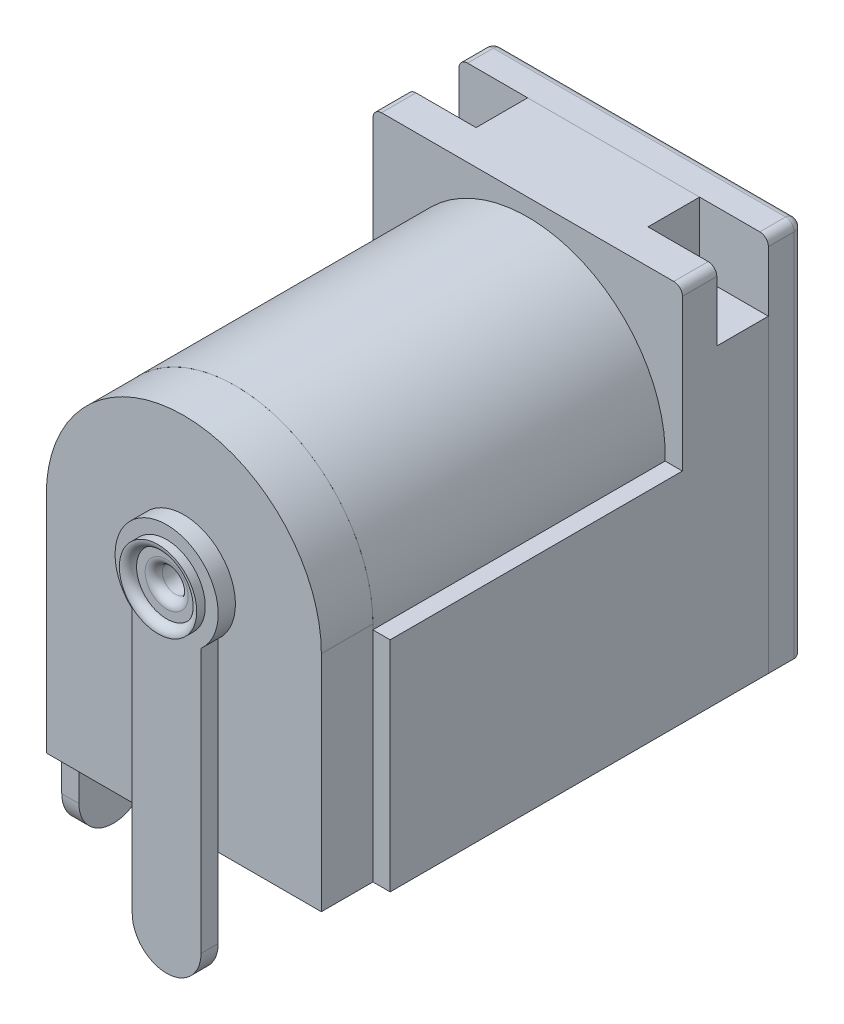
SolidWorks part; units mm, degrees
ref_plane "Front Plane" through (0, 0, 0) normal (0, 0, 1) x (1, 0, 0)
ref_plane "Top Plane" through (0, 0, 0) normal (0, 1, 0) x (1, 0, 0)
ref_plane "Right Plane" through (0, 0, 0) normal (1, 0, 0) x (0, 0, -1)
sketch "Sketch1" plane through (0, 0, 0) normal (0, 0, 1) x (1, 0, 0)
  line L1 (4.5, -3.175) -> (-4.5, -3.175)
  line L2 (4.5, -3.175) -> (4.5, 3.175)
  line L3 (4.5, 3.175) -> (-4.5, 3.175)
  line L4 (-4.5, -3.175) -> (-4.5, 3.175)
  line L5 (4.5, -3.175) -> (-4.5, 3.175) construction
  line L6 (4.5, 3.175) -> (-4.5, -3.175) construction
  point P0 (0, 0)
  dimension "D1" = 6.35
  dimension "D2" = 9
extrude "Boss-Extrude1" add sketch "Sketch1" along normal blind 12
sketch "Sketch2" plane through (0, 0, 0) normal (0, 0, -1) x (-1, 0, 0)
  line L1 (4.5, 7.825) -> (-4.5, 7.825)
  line L2 (4.5, 7.825) -> (4.5, -3.175)
  line L3 (4.5, -3.175) -> (-4.5, -3.175)
  line L4 (-4.5, 7.825) -> (-4.5, -3.175)
  line L5 (4.5, 7.825) -> (-4.5, -3.175) construction
  line L6 (4.5, -3.175) -> (-4.5, 7.825) construction
  point P0 (0, 2.325)
  dimension "D1" = 11
extrude "Boss-Extrude2" add sketch "Sketch2" against normal blind 3.5
sketch "Sketch4" plane through (0, 0, 0) normal (0, 0, -1) x (-1, 0, 0)
  line L1 (4.5, 7.825) -> (-4.5, 7.825) construction
  circle A0 centre (0, 3.325) radius 4
  point P6 (0, 7.325)
  dimension "D1" = 8
  dimension "D2" = 0.5
extrude "Boss-Extrude3" add sketch "Sketch4" against normal up to surface (12 mm away) up to face at (0, 0, 12)
ref_plane "Plane1" through (0, 0, 1.75) normal (0, 0, 1) x (1, 0, 0)
sketch "Sketch5" plane through (0, 0, 1.75) normal (0, 0, 1) x (1, 0, 0)
  line L0 (0, 0) -> (0, 7.825) construction
  line L1 (-2.5, 5.825) -> (-4.5, 5.825)
  line L2 (-2.5, 5.825) -> (-2.5, 7.825)
  line L3 (-2.5, 7.825) -> (-4.5, 7.825)
  line L4 (-4.5, 5.825) -> (-4.5, 7.825)
  line L5 (-2.5, 5.825) -> (-4.5, 7.825) construction
  line L6 (-2.5, 7.825) -> (-4.5, 5.825) construction
  line L7 (-4.5, 7.825) -> (4.5, 7.825) construction
  line L8 (2.5, 7.825) -> (4.5, 5.825) construction
  line L9 (2.5, 5.825) -> (4.5, 7.825) construction
  line L10 (4.5, 5.825) -> (4.5, 7.825)
  line L11 (2.5, 7.825) -> (4.5, 7.825)
  line L12 (2.5, 5.825) -> (2.5, 7.825)
  line L13 (2.5, 5.825) -> (4.5, 5.825)
  point P0 (-3.5, 6.825)
  point P16 (3.5, 6.825)
  dimension "D1" = 2
extrude "Cut-Extrude1" cut sketch "Sketch5" against normal mid plane 1.5
fillet "Fillet1" radius 0.25 8 edges at (0, -3.175, 0) (4.5, 2.325, 0) (0, 7.825, 0) (-4.5, 2.325, 0) (-4.5, 7.825, 0.5) (-4.5, 7.825, 3) (4.5, 7.825, 0.5) (4.5, 7.825, 3)
sketch "Sketch6" plane through (0, 0, 0) normal (0, 0, -1) x (-1, 0, 0)
  circle A0 centre (0, 3.325) radius 3.25
  dimension "D1" = 6.5
extrude "Cut-Extrude2" cut sketch "Sketch6" against normal up to next
sketch "Sketch7" plane through (0, 0, 12) normal (0, 0, 1) x (1, 0, 0)
  line L0 (-4.5, -3.175) -> (4.5, -3.175) construction
  line L1 (4, 1.325) -> (-4, 1.325)
  line L2 (4, 1.325) -> (4, -2.675)
  line L3 (4, -2.675) -> (-4, -2.675)
  line L4 (-4, 1.325) -> (-4, -2.675)
  line L5 (4, 1.325) -> (-4, -2.675) construction
  line L6 (4, -2.675) -> (-4, 1.325) construction
  line L7 (-4.5, 3.175) -> (-4.5, -3.175) construction
  point P0 (0, -0.675)
  dimension "D1" = 0.5
  dimension "D2" = 0.5
  dimension "D3" = 4
extrude "Cut-Extrude3" cut sketch "Sketch7" against normal up to surface (11 mm away) up to face at (3.6604, 6.9854, 1)
sketch "Sketch8" plane through (0, 0, 12) normal (0, 0, 1) x (1, 0, 0)
  line L0 (-4, 3.325) -> (-4, -3.175)
  line L1 (4, 3.325) -> (4, -3.175)
  line L2 (-4, -3.175) -> (4, -3.175)
  line L3 (-4.5, -3.175) -> (4.5, -3.175) construction
  arc A0 (-4, 3.325) -> (4, 3.325) centre (0, 3.325) cw
  arc A1 (3.9972, 3.175) -> (-3.9972, 3.175) centre (0, 3.325) ccw construction
extrude "Boss-Extrude5" add sketch "Sketch8" along normal blind 1.5 separate body
sketch "Sketch9" plane through (0, 7.825, 0) normal (0, 1, 0) x (1, 0, 0)
  line L0 (-5, -1) -> (5, -1)
  line L1 (4.25, -1) -> (4.5, -1) construction
  line L2 (0, -1) -> (0, 0) construction
  dimension "D1" = 10
split "Split1" trim tools "Sketch9" bodies to split 106 resulting bodies 111 112
sketch "Sketch10" plane through (0, 0, 13.5) normal (0, 0, 1) x (1, 0, 0)
  circle A0 centre (0, 3.325) radius 1.5
  dimension "D1" = 3
extrude "Cut-Extrude4" cut sketch "Sketch10" against normal through all
sketch "Sketch11" plane through (0, 0, 12) normal (0, 0, -1) x (-1, 0, 0)
  circle A0 centre (0, 3.325) radius 1.5
  dimension "D1" = 3
extrude "Boss-Extrude6" add sketch "Sketch11" against normal blind 2 separate body
sketch "Sketch12" plane through (0, 0, 12) normal (0, 0, -1) x (-1, 0, 0)
  circle A0 centre (0, 3.325) radius 0.75
  dimension "D1" = 1.5
extrude "Boss-Extrude7" add sketch "Sketch12" along normal offset from surface (11 mm away) 1 up to face at (-3.25, 3.325, 0)
fillet "Fillet2" radius 0.7 1 edges at (0.75, 3.325, 1) type face fillet first side face at (0.75, 3.325, 1) second side face at (0.75, 3.325, 1)
sketch "Sketch13" plane through (0, 0, 13.5) normal (0, 0, 1) x (1, 0, 0)
  line L0 (-1, 2.207) -> (-1, -5.475)
  line L4 (1, -5.475) -> (1, 2.207)
  line L5 (0, 3.325) -> (0, -6.475) construction
  line L6 (-4, -3.175) -> (4, -3.175) construction
  circle A0 centre (0, 3.325) radius 1.5 construction
  circle A1 centre (0, 3.325) radius 1.5 construction
  arc A2 (1, 2.207) -> (-1, 2.207) centre (0, 3.325) cw
  arc A3 (-1, -5.475) -> (1, -5.475) centre (0, -5.475) ccw
  dimension "D1" = 2
  dimension "D2" = 3.3
extrude "Boss-Extrude8" add sketch "Sketch13" along normal up to surface (0.5 mm away) up to face at (-1.5, 3.325, 14)
sketch "Sketch14" plane through (0, 0, 12) normal (0, 0, 1) x (1, 0, 0)
  line L0 (-4.5, 3.175) -> (-4.5, -3.175) construction
  line L1 (-4, 0.675) -> (-4.5, 0.675)
  line L2 (-4, 0.675) -> (-4, 1.175)
  line L3 (-4, 1.175) -> (-4.5, 1.175)
  line L4 (-4.5, 0.675) -> (-4.5, 1.175)
  line L5 (-4, 0.675) -> (-4.5, 1.175) construction
  line L6 (-4, 1.175) -> (-4.5, 0.675) construction
  line L7 (-4, 1.325) -> (-4, -2.675) construction
  line L8 (-3.9972, 3.175) -> (-4.5, 3.175) construction
  point P0 (-4.25, 0.925)
  dimension "D1" = 0.5
  dimension "D2" = 2
extrude "Cut-Extrude5" cut sketch "Sketch14" against normal blind 2
sketch "Sketch15" plane through (0, 0, 12) normal (0, 0, 1) x (1, 0, 0)
  line L0 (-3.5, 0.675) -> (-4.5, 0.675)
  line L1 (-4.5, 0.675) -> (-4.5, -3.175) construction
  line L2 (-4.55, 0.625) -> (-4.55, -3.175)
  line L3 (-4.5, -3.175) -> (4.5, -3.175) construction
  line L4 (-4.5, 0.675) -> (-4, 0.675) construction
  arc A0 (-4.5, 0.675) -> (-4.55, 0.625) centre (-4.5, 0.625) ccw
  dimension "D1" = 0.05
  dimension "D2" = 1
extrude "Extrude-Thin1" add sketch "Sketch15" against normal up to surface (2 mm away) separate body thin up to face at (-4.25, 0.925, 10) thin type one direction wall 0.5
sketch "Sketch16" plane through (-5.05, 0, 0) normal (-1, 0, 0) x (0, 0, 1)
  line L0 (10, -3.175) -> (10, -5.475)
  line L1 (12, -5.475) -> (12, -3.175)
  line L2 (10, -3.175) -> (12, -3.175)
  line L3 (13.5, -6.475) -> (11, -6.475) construction
  line L4 (13.5, -6.475) -> (14, -6.475) construction
  line L5 (13.5, -5.475) -> (13.5, -6.475) construction
  arc A0 (10, -5.475) -> (12, -5.475) centre (11, -5.475) ccw
  point P5 (11, -6.475)
extrude "Boss-Extrude9" add sketch "Sketch16" against normal up to surface (0.5 mm away) up to face at (-4.55, -1.275, 11)
ref_plane "Plane2" through (0, 0, 7.5) normal (0, 0, 1) x (1, 0, 0)
sketch "Sketch17" plane through (0, 0, 7.5) normal (0, 0, 1) x (1, 0, 0)
  line L0 (-1, -3.175) -> (-1, -5.475)
  line L1 (1, -5.475) -> (1, -3.175)
  line L2 (-4.5, -3.175) -> (4.5, -3.175) construction
  line L3 (1, -3.175) -> (-1, -3.175) construction
  line L4 (0, -5.475) -> (0, 0) construction
  line L5 (1, -3.175) -> (1, -1.675)
  line L6 (1, -1.675) -> (-1, -1.675)
  line L7 (-1, -1.675) -> (-1, -3.175)
  arc A0 (-1, -5.475) -> (1, -5.475) centre (0, -5.475) ccw
  arc A1 (-1, -5.475) -> (1, -5.475) centre (0, -5.475) ccw construction
  arc A2 (-1, -5.475) -> (1, -5.475) centre (0, -5.475) ccw construction
  dimension "D1" = 2
  dimension "D2" = 1.5
extrude "Boss-Extrude10" add sketch "Sketch17" against normal blind 0.5 separate body
sketch "Sketch18" plane through (0, 0, 0) normal (1, 0, 0) x (0, 0, -1)
  line L0 (-1, -2.675) -> (-1, -1.175)
  line L1 (-1.987, 0.2345) -> (-5.7457, 1.6026)
  line L2 (0, 7.575) -> (0, -2.925) construction
  line L4 (-1, -2.675) -> (-12, -2.675) construction
  line L5 (-6.2588, 0.1931) -> (-7.223, 1.3421) construction
  line L6 (-6.2588, 0.1931) -> (-5.7457, 1.6026) construction
  arc A0 (-1, -1.175) -> (-1.987, 0.2345) centre (-2.5, -1.175) ccw
  arc A1 (-5.7457, 1.6026) -> (-7.223, 1.3421) centre (-6.2588, 0.1931) ccw
  dimension "D3" = 1.5
  dimension "D6" = 1.5
  dimension "D1" = 1
  dimension "D2" = 1.5
  dimension "D4" = 70
  dimension "D5" = 4
  dimension "D7" = 60
extrude "Extrude-Thin2" add sketch "Sketch18" along normal mid plane 4 separate body thin thin type one direction reverse wall 0.5
sketch "Sketch21" plane through (0, 0, 14) normal (0, 0, 1) x (1, 0, 0)
  circle A0 centre (0, 3.325) radius 0.875
  circle A1 centre (0, 3.325) radius 1.5 construction
  circle A2 centre (0, 3.325) radius 1.5 construction
  dimension "D1" = 1.75
extrude "Extrude-Thin3" add sketch "Sketch21" along normal blind 0.25 thin thin type one direction wall 0.25
sketch "Sketch22" plane through (0, 0, 14) normal (0, 0, 1) x (1, 0, 0)
  circle A0 centre (0, 3.325) radius 0.375
  dimension "D1" = 0.75
extrude "Cut-Extrude6" cut sketch "Sketch22" against normal blind 3
fillet "Fillet3" radius 0.25 2 edges at (0.375, 3.325, 14) (0.875, 3.325, 14.25)
